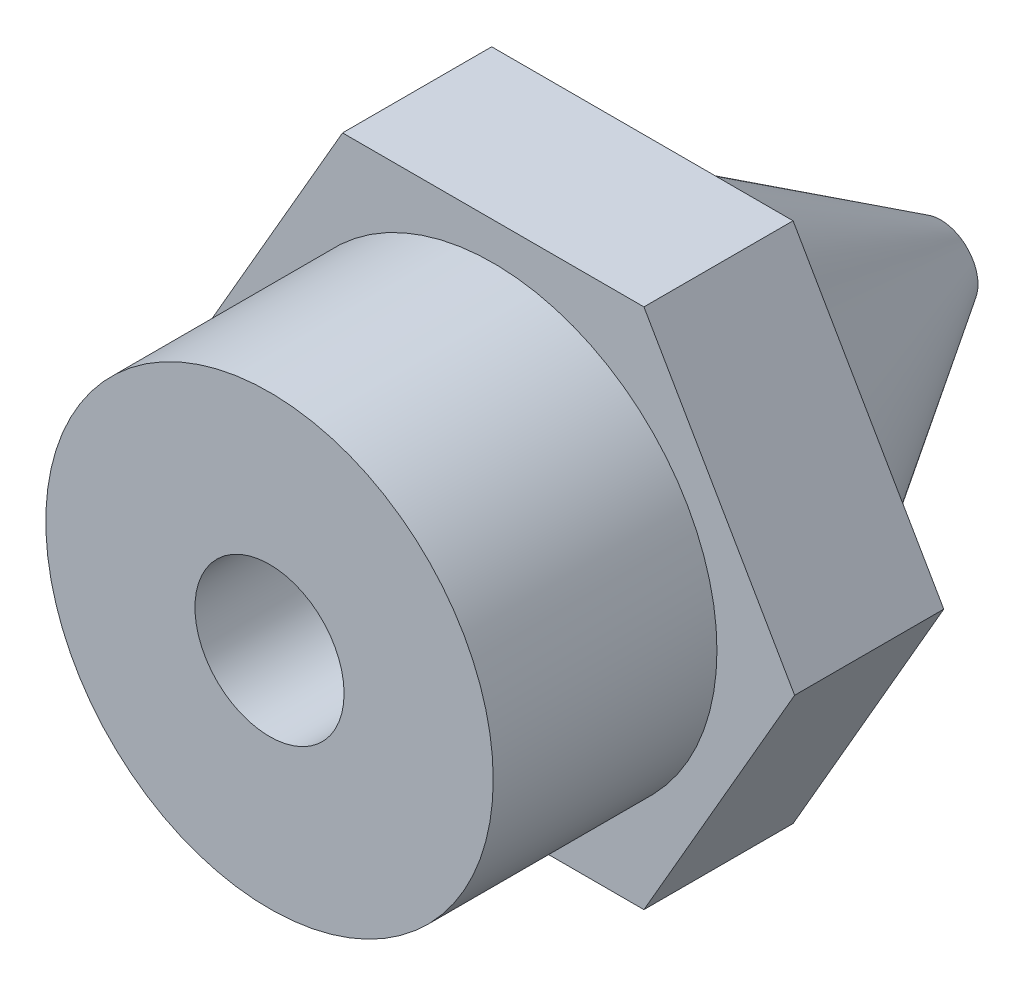
SolidWorks part; units mm, degrees
material "Laiton"
ref_plane "Plan de face" through (0, 0, 0) normal (0, 0, 1) x (1, 0, 0)
ref_plane "Plan de dessus" through (0, 0, 0) normal (0, 1, 0) x (1, 0, 0)
ref_plane "Plan de droite" through (0, 0, 0) normal (1, 0, 0) x (0, 0, -1)
sketch "Esquisse1" plane through (0, 0, 0) normal (0, 0, 1) x (1, 0, 0)
  line L1 (4.0415, 0) -> (2.0207, 3.5)
  line L2 (2.0207, 3.5) -> (-2.0207, 3.5)
  line L3 (-2.0207, 3.5) -> (-4.0415, 0)
  line L4 (-4.0415, 0) -> (-2.0207, -3.5)
  line L5 (-2.0207, -3.5) -> (2.0207, -3.5)
  line L6 (2.0207, -3.5) -> (4.0415, 0)
  circle A0 centre (0, 0) radius 3.5 construction
  dimension "D1" = 7
extrude "Boss.-Extru.1" add sketch "Esquisse1" along normal blind 9 contours L3 L4 L5 L6 L1 L2
sketch "Esquisse2" plane through (0, 0, 9) normal (0, 0, 1) x (1, 0, 0)
  line L1 (-9.4849, 6.2226) -> (10.1391, 6.2226)
  line L2 (-9.4849, 6.2226) -> (-9.4849, -9.3115)
  line L3 (-9.4849, -9.3115) -> (10.1391, -9.3115)
  line L4 (10.1391, 6.2226) -> (10.1391, -9.3115)
  circle A0 centre (0, 0) radius 3
  dimension "D1" = 6
extrude "Enlèv. mat.-Extru.1" cut sketch "Esquisse2" against normal blind 3
cosmetic thread "Représentation de filetage1" parameters "D1"=3, "D2"=4.891
sketch "Esquisse3" plane through (0, 0, 0) normal (0, 0, -1) x (-1, 0, 0)
  line L1 (5.6434, -6.9413) -> (-5.6238, -6.9413)
  line L2 (5.6434, -6.9413) -> (5.6434, 7.0198)
  line L3 (5.6434, 7.0198) -> (-5.6238, 7.0198)
  line L4 (-5.6238, -6.9413) -> (-5.6238, 7.0198)
  circle A0 centre (0, 0) radius 3
  dimension "D1" = 6
extrude "Enlèv. mat.-Extru.2" cut sketch "Esquisse3" against normal blind 4
chamfer "Chanfrein1" distance 4 angle 32 1 edges at (-3, 0, 0) first distance on face at (-3, 0, 4)
sketch "Esquisse4" plane through (0, 0, 0) normal (0, 1, 0) x (1, 0, 0)
  line L0 (0, -10.3816) -> (0, 2.1166) construction
  line L1 (0, -9) -> (1, -9)
  line L2 (-3, -9) -> (3, -9) construction
  line L3 (0, 0) -> (0.2, 0)
  line L4 (0.2, 0) -> (1, -6.5155)
  line L5 (0, -9) -> (0, 0)
  line L9 (1, -6.5155) -> (1, -9)
  dimension "D1" = 1
  dimension "D2" = 0.2
  dimension "D3" = 7
  dimension "D4" = 2.4845
revolve "Enlèvement de matière-Révolution1" cut sketch "Esquisse4" angle 360 about L0
